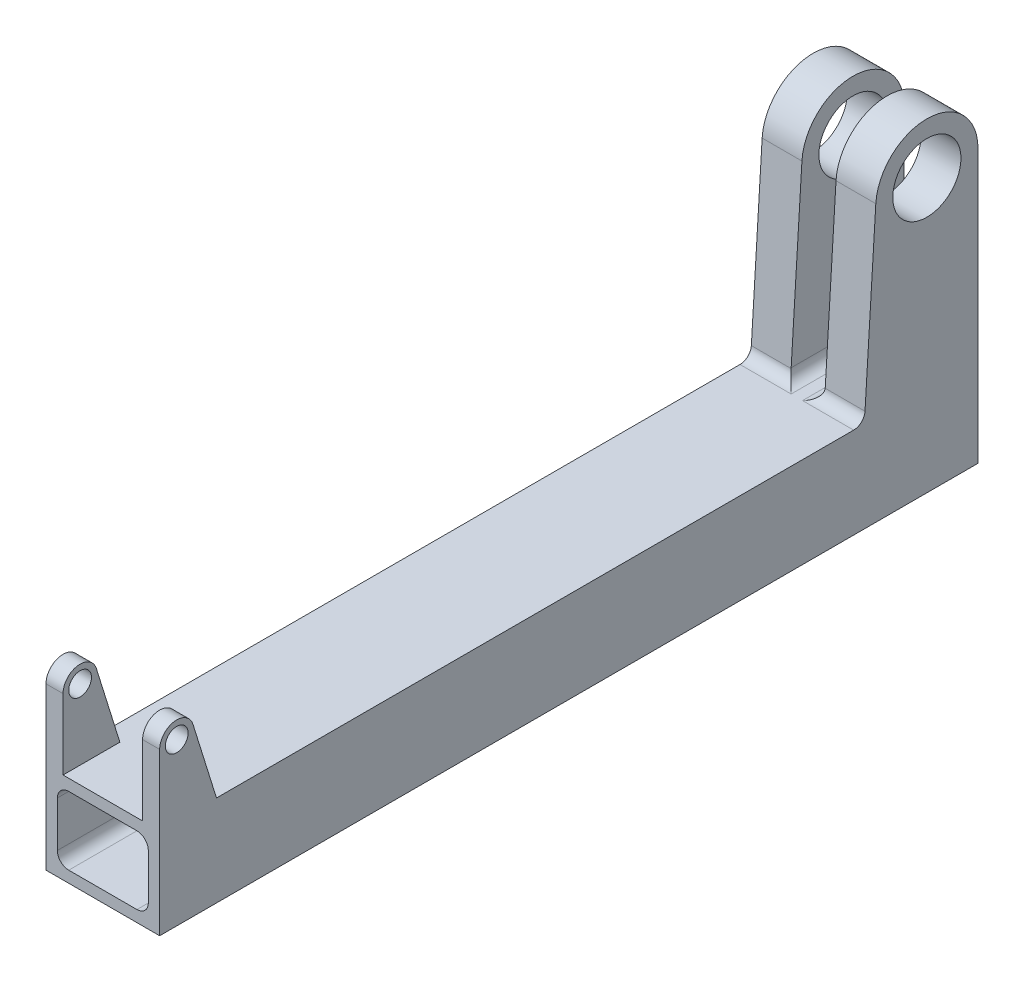
SolidWorks part; units mm, degrees
material "AISI 1045 Steel, cold drawn"
ref_plane "Front Plane" through (0, 0, 0) normal (0, 0, 1) x (1, 0, 0)
ref_plane "Top Plane" through (0, 0, 0) normal (0, 1, 0) x (1, 0, 0)
ref_plane "Right Plane" through (0, 0, 0) normal (1, 0, 0) x (0, 0, -1)
sketch "Sketch1" plane through (0, 0, 0) normal (1, 0, 0) x (0, 0, -1)
  line L0 (0, 0) -> (-914.4, 0)
  line L1 (-914.4, 0) -> (-914.4, 101.6)
  line L2 (-914.4, 101.6) -> (0, 101.6)
  line L3 (0, 101.6) -> (0, 0)
  line L4 (0, 101.6) -> (0, 304.8)
  line L5 (-114.1906, 308.3343) -> (-127, 101.6)
  arc A0 (0, 304.8) -> (-114.1906, 308.3343) centre (-57.15, 304.8) ccw
  circle A1 centre (-57.15, 304.8) radius 38.1
  point P8 (0, 0)
  point P10 (-122.5268, 50.8)
  point P11 (0, 0)
  dimension "D1" = 101.6
  dimension "D4" = 76.2
  dimension "D2" = 914.4
  dimension "D3" = 203.2
  dimension "D5" = 19.05
  dimension "D6" = 69.85
sketch "Sketch2" plane through (0, 0, 0) normal (0, 0, 1) x (1, 0, 0)
  line L0 (0, 101.6) -> (0, 0) construction
  line L1 (0, 101.6) -> (-127, 101.6)
  line L2 (0, 101.6) -> (0, 0)
  line L3 (0, 0) -> (-127, 0)
  line L4 (-127, 101.6) -> (-127, 0)
  line L5 (0, 101.6) -> (0, 304.8) construction
  line L6 (-12.7, 88.9) -> (-12.7, 12.7)
  line L7 (-12.7, 12.7) -> (-114.3, 12.7)
  line L8 (-114.3, 88.9) -> (-114.3, 12.7)
  line L9 (-12.7, 88.9) -> (-114.3, 88.9)
  point P8 (0, 0)
  dimension "D1" = 101.6
  dimension "D2" = 127
  dimension "D3" = 12.7
extrude "Boss-Extrude2" add sketch "Sketch2" along normal up to vertex (914.4 mm away) up to point (0, 101.6, 914.4)
extrude "Boss-Extrude3" add sketch "Sketch1" against normal blind 44.45 contours L4 A0 L5 L2 A1 region at (0, 208.7403, 60.3334)
ref_plane "Plane1" through (-127, 0, 0) normal (-1, 0, 0) x (0, 0, 1)
sketch "Sketch3" plane through (-127, 0, 0) normal (-1, 0, 0) x (0, 0, 1)
  line L3 (0, 304.8) -> (0, 101.6)
  line L4 (0, 101.6) -> (127, 101.6)
  line L5 (127, 101.6) -> (114.1906, 308.3343)
  line L6 (0, 304.8) -> (0, 101.6)
  line L7 (0, 101.6) -> (127, 101.6)
  line L8 (127, 101.6) -> (114.1906, 308.3343)
  circle A0 centre (57.15, 304.8) radius 38.1 construction
  arc A1 (114.1906, 308.3343) -> (0, 304.8) centre (57.15, 304.8) ccw
  arc A2 (114.1906, 308.3343) -> (0, 304.8) centre (57.15, 304.8) ccw
  circle A3 centre (57.15, 304.8) radius 38.1
  dimension "D1" = 0
extrude "Boss-Extrude5" add sketch "Sketch3" against normal blind 44.45
fillet "Fillet1" radius 12.7 4 edges at (-12.7, 12.7, 457.2) (-12.7, 88.9, 457.2) (-114.3, 88.9, 457.2) (-114.3, 12.7, 457.2)
fillet "Fillet2" radius 12.7 4 edges at (-104.775, 101.6, 127) (-22.225, 101.6, 127) (-82.55, 101.6, 63.5) (-44.45, 101.6, 63.5)
sketch "Sketch5" plane through (0, 0, 0) normal (1, 0, 0) x (0, 0, -1)
  line L0 (-914.4, 101.6) -> (-914.4, 180.34)
  line L1 (-877.1601, 185.9996) -> (-850.9, 101.6)
  line L2 (-914.4, 101.6) -> (-138.9375, 101.6) construction
  line L3 (-850.9, 101.6) -> (-914.4, 101.6)
  arc A0 (-914.4, 180.34) -> (-877.1601, 185.9996) centre (-895.35, 180.34) cw
  circle A1 centre (-895.35, 180.34) radius 12.7
  dimension "D3" = 6.35
  dimension "D4" = 25.4
  dimension "D1" = 78.74
  dimension "D2" = 63.5
extrude "Boss-Extrude7" add sketch "Sketch5" against normal blind 19.05
pattern_linear "LPattern1" count 2 spacing 107.95 along (-1, 0, 0) of "Boss-Extrude7"
equation "\"D1@Sketch2\"=\"D1@Sketch1\""
